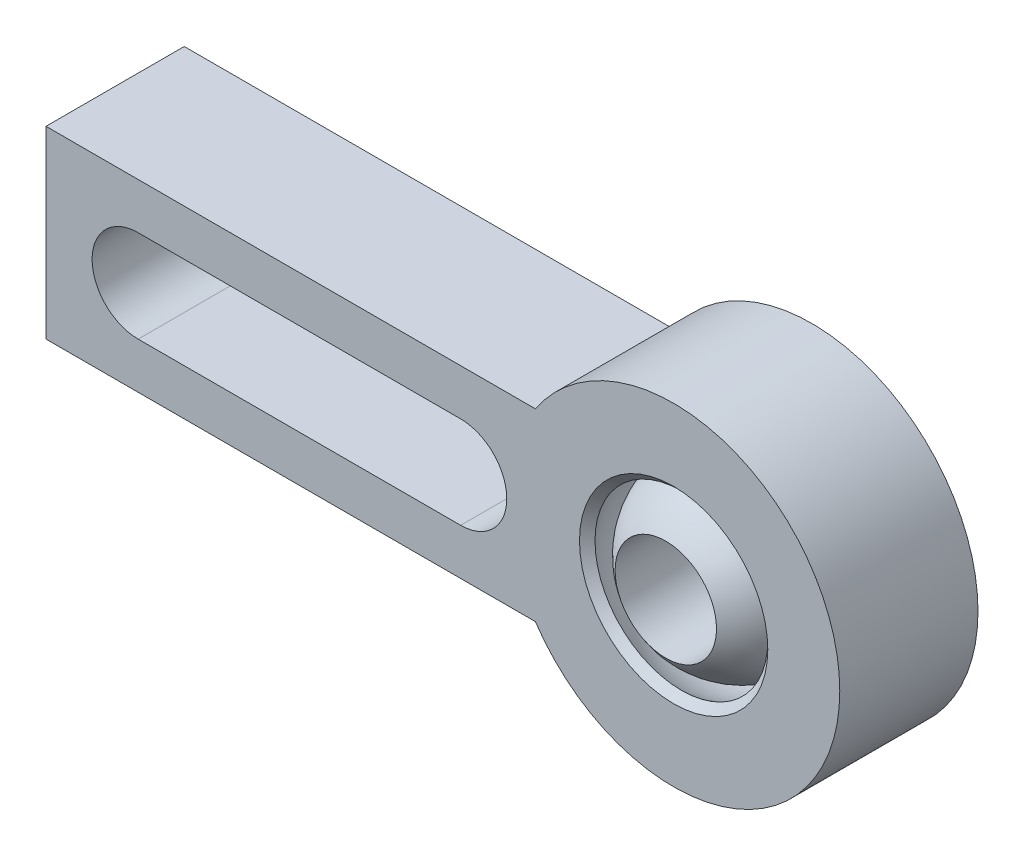
SolidWorks part; units mm, degrees
ref_plane "Front Plane" through (0, 0, 0) normal (0, 0, 1) x (1, 0, 0)
ref_plane "Top Plane" through (0, 0, 0) normal (0, 1, 0) x (1, 0, 0)
ref_plane "Right Plane" through (0, 0, 0) normal (1, 0, 0) x (0, 0, -1)
sketch "Sketch1" plane through (0, 0, 0) normal (0, 0, 1) x (1, 0, 0)
  line L4 (2.4014, 9.6997) -> (2.4014, -0.4603) construction
  line L6 (-24.5786, 9.6997) -> (-24.5786, -0.4603)
  line L7 (10.0214, 10.4617) -> (10.0214, -1.2223)
  line L10 (2.4014, 9.6997) -> (-24.5786, 9.6997)
  line L12 (2.4014, -0.4603) -> (-24.5786, -0.4603)
  line L17 (-11.0886, 9.6997) -> (-11.0886, -0.4603) construction
  line L20 (-19.4986, 4.6197) -> (-1.7186, 4.6197) construction
  line L21 (-19.4986, 7.1597) -> (-1.7186, 7.1597)
  line L22 (-19.4986, 2.0797) -> (-1.7186, 2.0797)
  arc A0 (2.4014, 9.6997) -> (2.4014, -0.4603) centre (10.0214, 4.6197) cw
  arc A3 (10.0214, 9.6997) -> (10.0214, -0.4603) centre (10.0214, 4.6197) ccw
  arc A4 (10.0214, 10.4617) -> (10.0214, -1.2223) centre (10.0214, 4.6197) ccw
  circle A5 centre (10.0214, 4.6197) radius 2.794
  arc A6 (-19.4986, 7.1597) -> (-19.4986, 2.0797) centre (-19.4986, 4.6197) ccw
  arc A7 (-1.7186, 2.0797) -> (-1.7186, 7.1597) centre (-1.7186, 4.6197) ccw
  point P14 (-12.6328, 6.0507)
  point P15 (-10.6086, 4.6197)
  dimension "D4" = 0.762
  dimension "D5" = 5.08
  dimension "D6" = 5.588
  dimension "D7" = 17.78
  dimension "D8" = 5.08
  dimension "D1" = 5.08
  dimension "D3" = 7.62
  dimension "D9" = 10.16
extrude "Boss-Extrude2" add sketch "Sketch1" along normal mid plane 7.62 separate body contours A0 | A0 L12 L6 L10 | L22 A7 L21 A6 region at (-11.0886, 9.2254, 0)
revolve "Cut-Revolve9" cut sketch "Sketch1<11>" angle 360 about L7
sketch "Sketch1<11>" plane through (0, 0, 0) normal (0, 0, 1) x (1, 0, 0) same geometry as "Sketch1"
revolve "Revolve7" add sketch "Sketch1<12>" angle 360 about L7 region at (9.9078, 8.5567, 0)
sketch "Sketch1<12>" plane through (0, 0, 0) normal (0, 0, 1) x (1, 0, 0) same geometry as "Sketch1"
extrude "Cut-Extrude1" cut sketch "Sketch1<13>" against normal through all both and the other way through all contours L7 A5 | L7 A5 region at (11.2072, 4.6197, 0) region at (8.8356, 4.6197, 0)
sketch "Sketch1<13>" plane through (0, 0, 0) normal (0, 0, 1) x (1, 0, 0) same geometry as "Sketch1"
chamfer "Chamfer2" distance 0.762 angle 45 2 edges at (14.45, 4.6197, -3.81) (14.45, 4.6197, 3.81) first distance on face at (14.45, 4.6197, 3.81)
